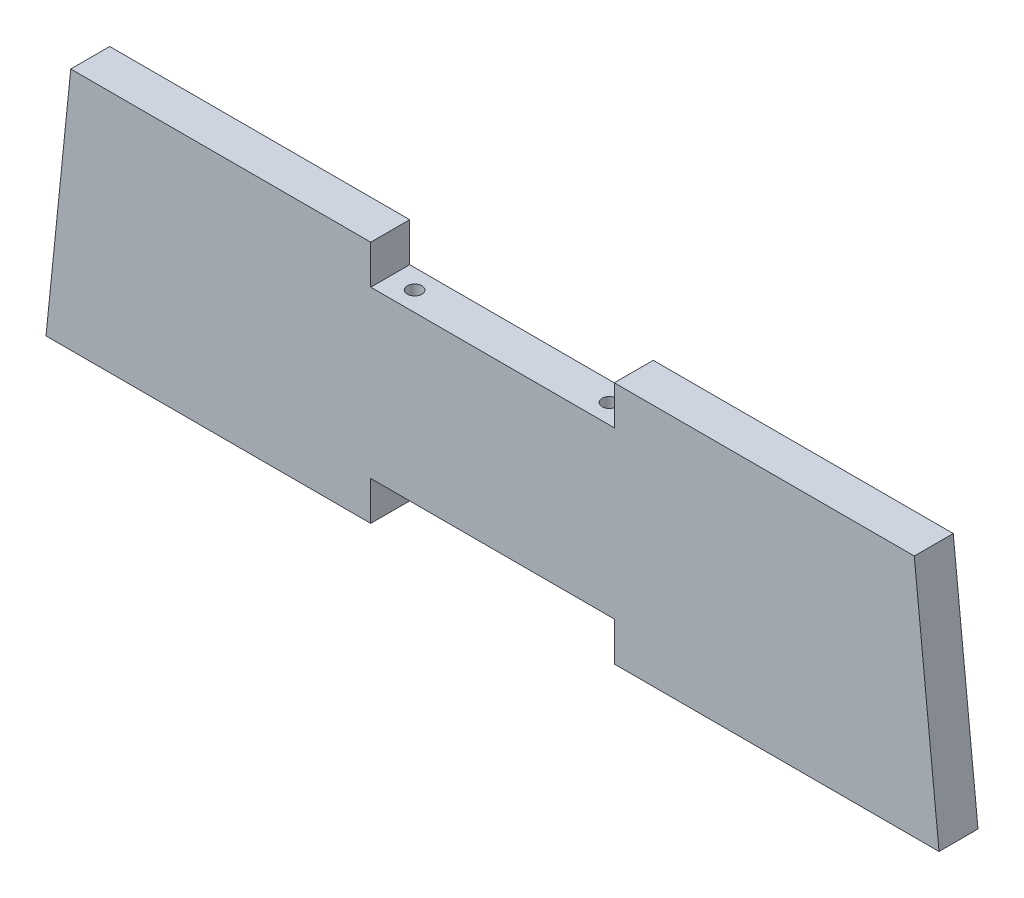
SolidWorks part; units mm, degrees
material "Acrylic (Medium-high impact)"
ref_plane "Front Plane" through (0, 0, 0) normal (0, 0, 1) x (1, 0, 0)
ref_plane "Top Plane" through (0, 0, 0) normal (0, 1, 0) x (1, 0, 0)
ref_plane "Right Plane" through (0, 0, 0) normal (1, 0, 0) x (0, 0, -1)
sketch "Chassi Outline Sketch" plane through (0, 0, 0) normal (0, 0, 1) x (1, 0, 0)
  line L0 (0, 0) -> (0, 128) construction
  line L1 (0, 0) -> (109.2209, 0) construction
  line L2 (91.6709, 0) -> (85.17, 64) construction
  line L3 (85.17, 64) -> (-85.17, 64) construction
  line L4 (85.17, 75.9083) -> (85.17, 0) construction
  line L5 (-91.6709, 0) -> (-85.17, 64) construction
  line L6 (0, 0) -> (-164.8351, 0) construction
  point P11 (0, 64)
  dimension "D1" = 5.8
  dimension "D2" = 85.17
  dimension "D3" = 64
  dimension "D4" = 183.3418
  dimension "D5" = 170.34
sketch "Chassi Outline Round Sketch" plane through (0, 0, 0) normal (0, 1, 0) x (1, 0, 0)
  circle A0 centre (0, 0) radius 91.6709 construction
sketch "Sketch2" plane through (0, 0, 0) normal (0, 0, 1) x (1, 0, 0)
  line L0 (-86.5921, 50) -> (86.5921, 50)
  line L1 (86.5921, 50) -> (91.6709, 0)
  line L2 (91.6709, 0) -> (-91.6709, 0)
  line L3 (0, 147.6601) -> (0, -41.9695) construction
  line L4 (-86.5921, 50) -> (-91.6709, 0)
  line L6 (91.6709, 0) -> (85.17, 64) construction
  line L7 (85.17, 64) -> (-85.17, 64) construction
  point P11 (0, 0)
  point P12 (0, 50)
  dimension "D1" = 14
extrude "Side Boss-Extrude1" add sketch "Sketch2" along normal blind 4 and the other way blind 4
sketch "Sketch3" plane through (0, 0, 4) normal (0, 0, 1) x (1, 0, 0)
  line L0 (0, 90.3714) -> (0, -16.6563) construction
  line L1 (-25, 0) -> (25, 0)
  line L2 (0, 0) -> (0, 128) construction
  line L3 (-25, 8) -> (25, 8)
  line L4 (25, 0) -> (25, 8)
  line L5 (-25, 0) -> (-25, 8)
  line L6 (25, 42) -> (0, 42)
  line L7 (0, 42) -> (-25, 42)
  line L9 (25, 42) -> (25, 50)
  line L10 (25, 50) -> (-25, 50)
  line L11 (86.5921, 50) -> (-86.5921, 50) construction
  line L12 (-25, 42) -> (-25, 50)
  point P11 (0, 8)
  point P12 (0, 0)
  dimension "D1" = 50
  dimension "D2" = 8
extrude "Socket Top And Bottom Cut-Extrude1" cut sketch "Sketch3" against normal up to surface (8 mm away) up to face at (0, 25, -4)
sketch "Sketch4" plane through (0, 42, 0) normal (0, 1, 0) x (1, 0, 0)
  line L0 (0, 0) -> (20, 0) construction
  line L1 (0, 0) -> (-20, 0) construction
  line L2 (25, 4) -> (25, -4) construction
  circle A0 centre (20, 0) radius 1.5
  circle A1 centre (-20, 0) radius 1.5
  dimension "D2" = 3
  dimension "D1" = 5
extrude "Mounting Holes Top Cut-Extrude2" cut sketch "Sketch4" against normal blind 10
sketch "Sketch5" plane through (0, 8, 0) normal (0, -1, 0) x (1, 0, 0)
  line L0 (0, 0) -> (20, 0) construction
  line L1 (0, 0) -> (-20, 0) construction
  line L2 (25, -4) -> (25, 4) construction
  circle A0 centre (20, 0) radius 1.5
  circle A1 centre (-20, 0) radius 1.5
  dimension "D2" = 3
  dimension "D1" = 5
extrude "Mounting Holes Bottom Cut-Extrude3" cut sketch "Sketch5" against normal blind 10
